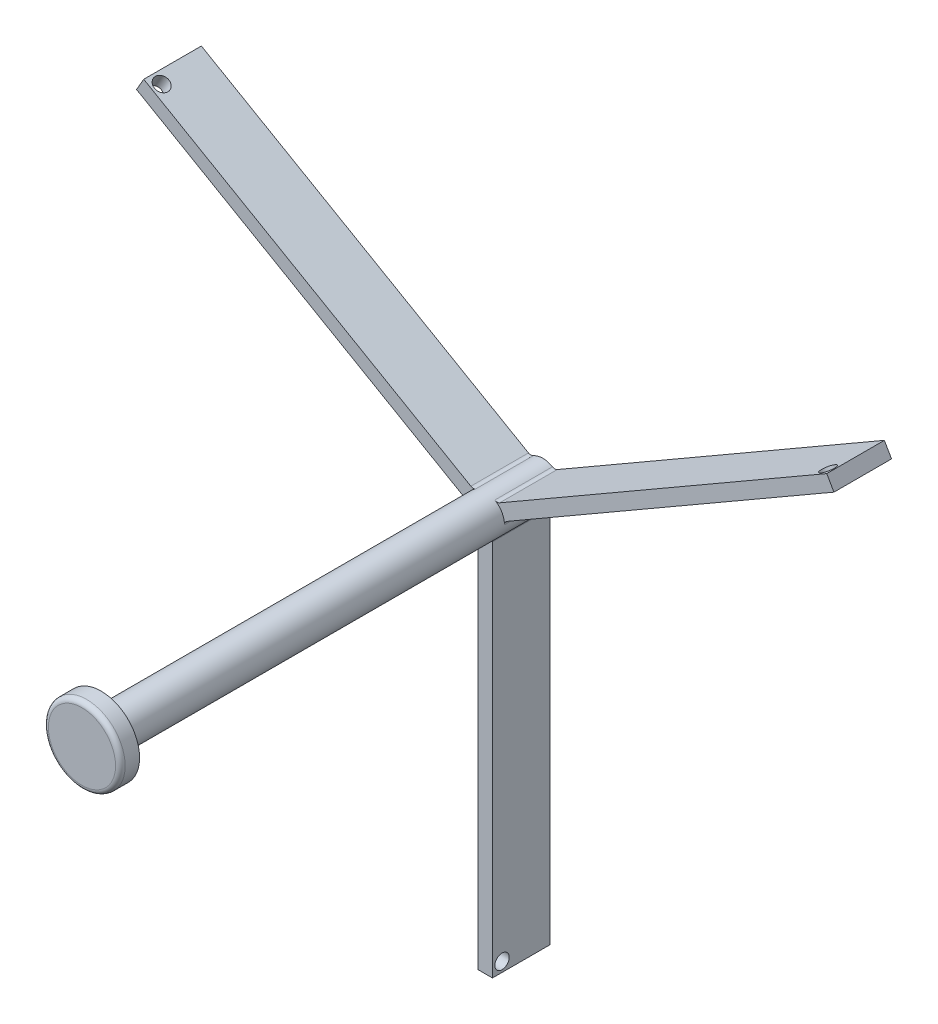
SolidWorks part; units mm, degrees
ref_plane "Plane1" through (0, 0, 0) normal (0, 0, 1) x (1, 0, 0)
ref_plane "Plane2" through (0, 0, 0) normal (0, 1, 0) x (1, 0, 0)
ref_plane "Plane3" through (0, 0, 0) normal (1, 0, 0) x (0, 0, -1)
other "Configuration Table"
sketch "Sketch1" plane through (0, 0, 0) normal (0, 0, 1) x (1, 0, 0)
  circle A0 centre (0, 0) radius 12.7
  dimension "D1" = 25.4
extrude "Base-Extrude" add sketch "Sketch1" along normal blind 304.8
sketch "Sketch2" plane through (0, 0, 0) normal (0, 1, 0) x (1, 0, 0)
  line L0 (0, 0) -> (0, -56.9618) construction
  line L1 (4.7625, 0) -> (-4.7625, 0)
  line L2 (12.7, 0) -> (-12.7, 0) construction
  line L3 (-4.7625, 0) -> (-4.7625, -38.1)
  line L4 (4.7625, 0) -> (4.7625, -38.1)
  line L5 (-4.7625, -38.1) -> (4.7625, -38.1)
  point P7 (0, 0)
  point P11 (0, -38.1)
  dimension "D1" = 38.1
  dimension "D2" = 9.525
extrude "Boss-Extrude1" add sketch "Sketch2" against normal blind 263.525
sketch "Sketch3" plane through (-4.7625, 0, 0) normal (-1, 0, 0) x (0, 0, 1)
  line L0 (0, -263.525) -> (38.1, -263.525) construction
  line L1 (38.1, -263.525) -> (38.1, -11.7732) construction
  circle A0 centre (31.75, -257.175) radius 4.7625
  dimension "D1" = 9.525
  dimension "D2" = 6.35
  dimension "D3" = 6.35
extrude "Cut-Extrude1" cut sketch "Sketch3" against normal through all
pattern_circular "CirPattern1" count 3 every 120 about axis through (0, 0, 304.8) along (0, 0, -1) of "Boss-Extrude1"
sketch "Sketch4" plane through (-194.3928, 106.7334, 225.0677) normal (-0.5, -0.866, 0) x (0.866, -0.5, 0)
  line L0 (-41.8092, -225.0677) -> (-41.8092, -186.9677) construction
  line L1 (-41.8092, -186.9677) -> (209.9426, -186.9677) construction
  circle A0 centre (-35.4592, -193.3177) radius 4.7625
  dimension "D1" = 9.525
  dimension "D2" = 6.35
  dimension "D3" = 6.35
extrude "Cut-Extrude2" cut sketch "Sketch4" against normal through all
sketch "Sketch5" plane through (132.0101, 70.7168, 223.486) normal (0.5, -0.866, 0) x (0.866, 0.5, 0)
  line L0 (113.8425, -223.486) -> (113.8425, -185.386) construction
  line L1 (113.8425, -185.386) -> (-137.9093, -185.386) construction
  circle A0 centre (107.4925, -191.736) radius 4.7625
  dimension "D1" = 9.525
  dimension "D2" = 6.35
  dimension "D3" = 6.35
extrude "Cut-Extrude3" cut sketch "Sketch5" against normal through all
hole_wizard "Hole1" positions "Sketch7" profile "Sketch8" legacy
sketch "Sketch7" plane through (0, 0, 0) normal (0, 0, -1) x (-1, 0, 0)
  point P0 (0, -63.5)
  dimension "D1" = 63.5
sketch "Sketch8" plane through (0, -63.5, 0) normal (1, 0, 0) x (0, 1, 0)
  line L0 (0, 0) -> (0, 8.6166)
  line L1 (0, 8.6166) -> (1.1303, 7.9375)
  line L2 (1.1303, 7.9375) -> (1.1303, 6.35)
  line L3 (1.1303, 6.35) -> (1.4224, 6.35)
  line L4 (1.4224, 6.35) -> (1.4224, 0.0025)
  line L5 (1.4224, 0.0025) -> (1.4224, 0)
  line L6 (1.4224, 0) -> (0, 0)
hole_wizard "Hole2" positions "Sketch9" profile "Sketch10" legacy
sketch "Sketch9" plane through (0, 0, 0) normal (0, 0, -1) x (-1, 0, 0)
  point P0 (0, -139.7)
  dimension "D1" = 139.7
sketch "Sketch10" plane through (0, -139.7, 0) normal (1, 0, 0) x (0, 1, 0)
  line L0 (0, 0) -> (0, 8.6166)
  line L1 (0, 8.6166) -> (1.1303, 7.9375)
  line L2 (1.1303, 7.9375) -> (1.1303, 6.35)
  line L3 (1.1303, 6.35) -> (1.4224, 6.35)
  line L4 (1.4224, 6.35) -> (1.4224, 0.0025)
  line L5 (1.4224, 0.0025) -> (1.4224, 0)
  line L6 (1.4224, 0) -> (0, 0)
hole_wizard "Hole3" positions "Sketch11" profile "Sketch12" legacy
sketch "Sketch11" plane through (0, 0, 0) normal (0, 0, -1) x (-1, 0, 0)
  point P0 (0, -215.9)
  dimension "D1" = 215.9
sketch "Sketch12" plane through (0, -215.9, 0) normal (1, 0, 0) x (0, 1, 0)
  line L0 (0, 0) -> (0, 8.6166)
  line L1 (0, 8.6166) -> (1.1303, 7.9375)
  line L2 (1.1303, 7.9375) -> (1.1303, 6.35)
  line L3 (1.1303, 6.35) -> (1.4224, 6.35)
  line L4 (1.4224, 6.35) -> (1.4224, 0.0025)
  line L5 (1.4224, 0.0025) -> (1.4224, 0)
  line L6 (1.4224, 0) -> (0, 0)
pattern_circular "CirPattern2" count 3 every 120 about axis through (0, 0, 304.8) along (0, 0, -1) of "Hole3", "Hole2", "Hole1"
fillet "Fillet1" radius 3.175 2 edges at (-12.5772, 1.7622, 19.05) (-4.7625, -11.7732, 19.05)
fillet "Fillet2" radius 3.175 2 edges at (-7.8147, 10.0111, 19.05) (7.8147, 10.0111, 19.05)
fillet "Fillet3" radius 3.175 2 edges at (4.7625, -11.7732, 19.05) (12.5772, 1.7622, 19.05)
sketch "Sketch13" plane through (0, 0, 304.8) normal (0, 0, 1) x (1, 0, 0)
  circle A0 centre (0, 0) radius 25.4
  circle A3 centre (0, 0) radius 12.7 construction
  dimension "D1" = 12.7
extrude "Extrude1" add sketch "Sketch13" against normal blind 12.7
fillet "Fillet4" radius 3.175 1 edges at (25.4, 0, 304.8)
